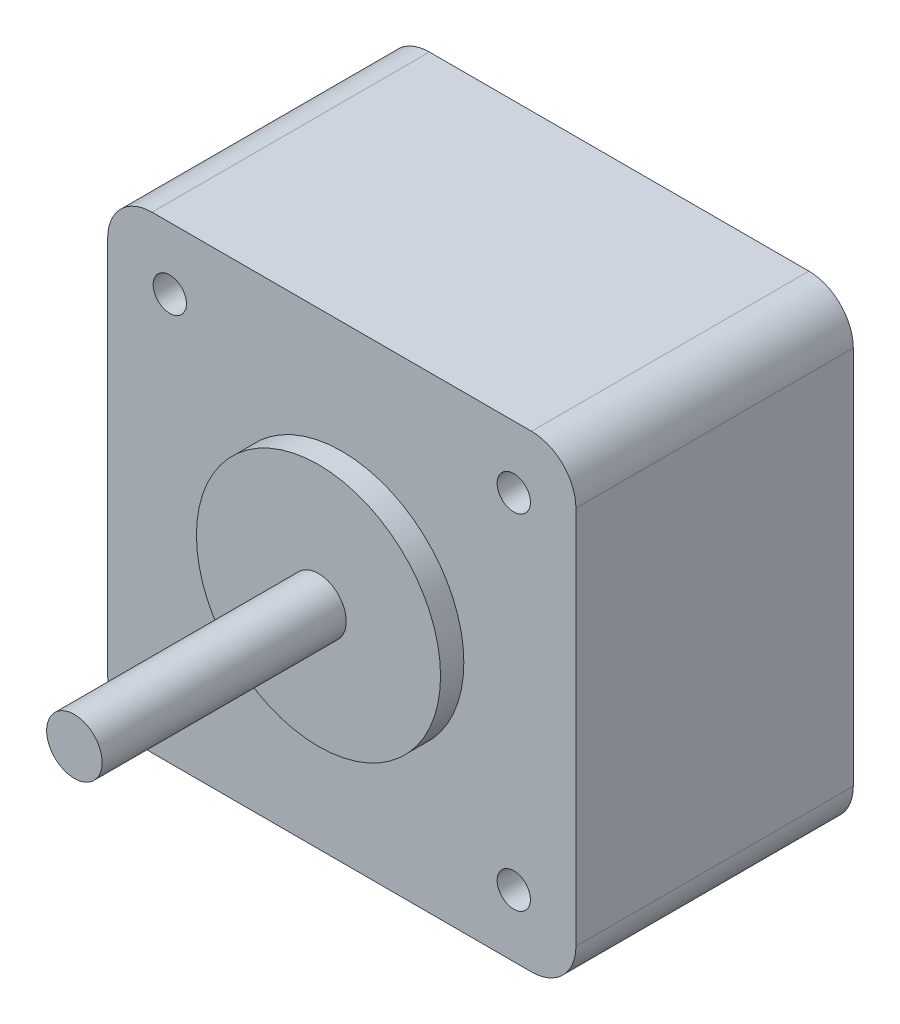
SolidWorks part; units mm, degrees
ref_plane "Ebene vorne" through (0, 0, 0) normal (0, 0, 1) x (1, 0, 0)
ref_plane "Ebene oben" through (0, 0, 0) normal (0, 1, 0) x (1, 0, 0)
ref_plane "Ebene rechts" through (0, 0, 0) normal (1, 0, 0) x (0, 0, -1)
sketch "Skizze1" plane through (0, 0, 0) normal (0, 0, 1) x (1, 0, 0)
  line L1 (-21.1, -21.1) -> (21.1, -21.1)
  line L2 (-21.1, -21.1) -> (-21.1, 21.1)
  line L3 (-21.1, 21.1) -> (21.1, 21.1)
  line L4 (21.1, -21.1) -> (21.1, 21.1)
  line L5 (-21.1, -21.1) -> (21.1, 21.1) construction
  line L6 (-21.1, 21.1) -> (21.1, -21.1) construction
  point P0 (0, 0)
  dimension "D1" = 42.2
extrude "Aufsatz-Linear austragen1" add sketch "Skizze1" along normal blind 25
sketch "Skizze2" plane through (0, 0, 25) normal (0, 0, 1) x (1, 0, 0)
  circle A0 centre (0, 0) radius 11
  dimension "D1" = 22
extrude "Aufsatz-Linear austragen2" add sketch "Skizze2" along normal blind 2.1
sketch "Skizze3" plane through (0, 0, 27.1) normal (0, 0, 1) x (1, 0, 0)
  circle A0 centre (0, 0) radius 2.5
  dimension "D1" = 5
extrude "Aufsatz-Linear austragen3" add sketch "Skizze3" along normal blind 22
sketch "Skizze4" plane through (0, 0, 25) normal (0, 0, 1) x (1, 0, 0)
  line L1 (-15.5, -15.5) -> (15.5, -15.5) construction
  line L2 (-15.5, -15.5) -> (-15.5, 15.5) construction
  line L3 (-15.5, 15.5) -> (15.5, 15.5) construction
  line L4 (15.5, -15.5) -> (15.5, 15.5) construction
  line L5 (-15.5, -15.5) -> (15.5, 15.5) construction
  line L6 (-15.5, 15.5) -> (15.5, -15.5) construction
  circle A0 centre (-15.5, 15.5) radius 1.5
  circle A1 centre (15.5, 15.5) radius 1.5
  circle A2 centre (15.5, -15.5) radius 1.5
  circle A3 centre (-15.5, -15.5) radius 1.5
  point P0 (0, 0)
  dimension "D3" = 3
  dimension "D1" = 31
  dimension "D2" = 31
extrude "Schnitt-Linear austragen1" cut sketch "Skizze4" against normal blind 4
ref_axis "Axis1" through (0, 0, 49.1) along (0, 0, -1)
ref_axis "Axis2" through (0, 0, 49.1) along (0, 0, -1)
fillet "Fillet1" radius 4 4 edges at (21.1, -21.1, 12.5) (-21.1, 21.1, 12.5) (21.1, 21.1, 12.5) (-21.1, -21.1, 12.5)
